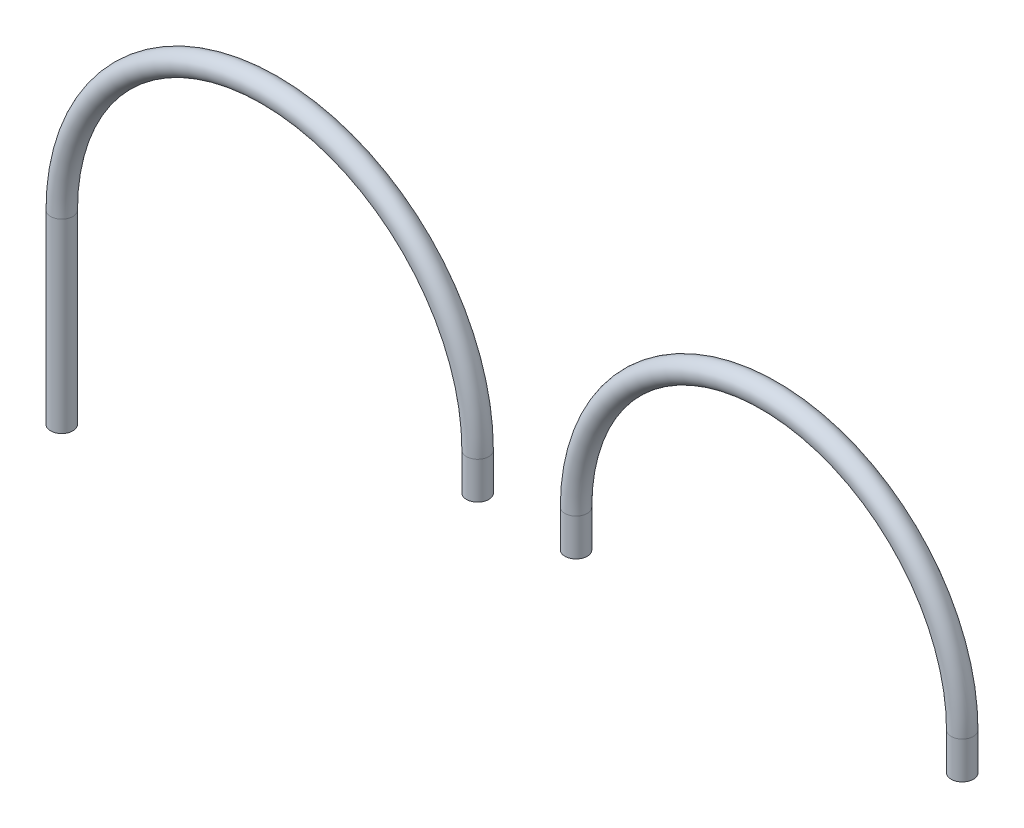
SolidWorks part; units mm, degrees
ref_plane "Plano frontal" through (0, 0, 0) normal (0, 0, 1) x (1, 0, 0)
ref_plane "Plano superior" through (0, 0, 0) normal (0, 1, 0) x (1, 0, 0)
ref_plane "Plano direito" through (0, 0, 0) normal (1, 0, 0) x (0, 0, -1)
sketch "Sketch1" plane through (0, 0, 0) normal (0, 0, 1) x (1, 0, 0)
  line L0 (-1348.4595, 0) -> (-1348.4595, -250)
  line L1 (-1068.4595, 0) -> (0, 0) construction
  line L2 (-788.4595, 0) -> (-788.4595, -50)
  arc A0 (-1348.4595, 0) -> (-788.4595, 0) centre (-1068.4595, 0) cw
  dimension "D1" = 280
  dimension "D3" = 50
  dimension "D2" = 250
sweep "Sweep-Thin1" add path "Sketch1" circular profile diameter 30 parameters "D1"=1, "D3"=30
sketch "Sketch28" plane through (0, 0, 0) normal (0, 0, 1) x (1, 0, 0)
  line L0 (-395.9551, 0) -> (0, 0) construction
  line L1 (-655.9551, 0) -> (-655.9551, -50)
  line L2 (-135.9551, 0) -> (-135.9551, -50)
  arc A0 (-655.9551, 0) -> (-135.9551, 0) centre (-395.9551, 0) cw
  dimension "D1" = 260
  dimension "D2" = 50
sweep "Sweep-Thin5" add path "Sketch28" circular profile diameter 30 parameters "D1"=1, "D3"=30
